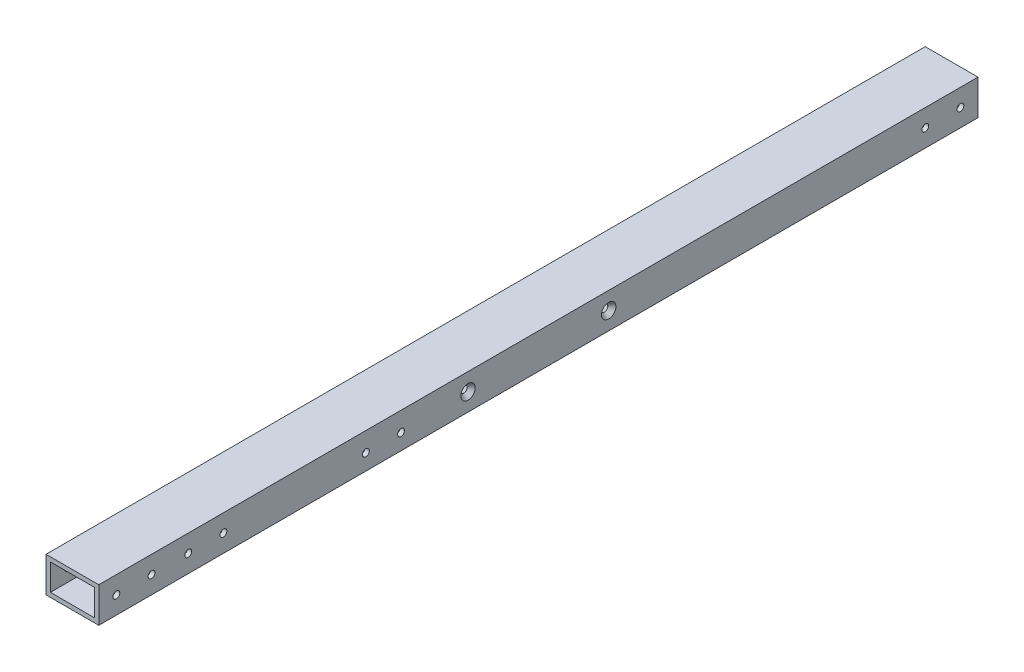
SolidWorks part; units mm, degrees
ref_plane "Front Plane" through (0, 0, 0) normal (0, 0, 1) x (1, 0, 0)
ref_plane "Top Plane" through (0, 0, 0) normal (0, 1, 0) x (1, 0, 0)
ref_plane "Right Plane" through (0, 0, 0) normal (1, 0, 0) x (0, 0, -1)
sketch "Sketch1" plane through (0, 0, 0) normal (0, 0, 1) x (1, 0, 0)
  line L0 (-15.875, 9.525) -> (15.875, 9.525)
  line L2 (-19.05, 12.7) -> (19.05, 12.7)
  line L3 (-19.05, 12.7) -> (-19.05, -12.7)
  line L4 (-19.05, -12.7) -> (19.05, -12.7)
  line L5 (19.05, 12.7) -> (19.05, -12.7)
  line L10 (15.875, 9.525) -> (15.875, -9.525)
  line L11 (-15.875, -9.525) -> (15.875, -9.525)
  line L12 (-15.875, 9.525) -> (-15.875, -9.525)
  point P12 (0, 12.7)
  point P14 (19.05, 0)
  dimension "Wall Thickness" = 3.175
  dimension "Outside Width" = 38.1
  dimension "Outside Height" = 25.4
  dimension "Inside Height" = 19.05
  dimension "Inside Width" = 31.75
sketch "Sketch2" plane through (0, 0, 0) normal (1, 0, 0) x (0, 0, -1)
  line L0 (317.5, 0) -> (-317.5, 0)
  point P4 (0, 0)
  point P7 (-317.5, 0)
  point P10 (317.5, 0)
  dimension "Length" = 635
sketch "Sketch3" plane through (0, 0, 0) normal (0, 0, 1) x (1, 0, 0)
  line L21 (19.05, 12.7) -> (-19.05, 12.7)
  line L22 (19.05, -12.7) -> (19.05, 12.7)
  line L23 (-19.05, -12.7) -> (19.05, -12.7)
  line L24 (-19.05, 12.7) -> (-19.05, -12.7)
  line L25 (19.05, 12.7) -> (-19.05, 12.7)
  line L26 (19.05, -12.7) -> (19.05, 12.7)
  line L27 (-19.05, -12.7) -> (19.05, -12.7)
  line L28 (-19.05, 12.7) -> (-19.05, -12.7)
  line L29 (15.875, 9.525) -> (-15.875, 9.525)
  line L30 (15.875, -9.525) -> (15.875, 9.525)
  line L31 (-15.875, -9.525) -> (15.875, -9.525)
  line L32 (-15.875, 9.525) -> (-15.875, -9.525)
  line L33 (15.875, 9.525) -> (-15.875, 9.525)
  line L34 (15.875, -9.525) -> (15.875, 9.525)
  line L35 (-15.875, -9.525) -> (15.875, -9.525)
  line L36 (-15.875, 9.525) -> (-15.875, -9.525)
  dimension "D1" = 0
  dimension "D2" = 0
extrude "Boss-Extrude1" add sketch "Sketch3" along normal up to vertex (317.5 mm away) and the other way up to vertex (317.5 mm away) up to point (0, 0, 317.5) other way up to point (0, 0, -317.5)
sketch "Drawing Reference" plane through (0, 0, 0) normal (1, 0, 0) x (0, 0, -1)
  line L0 (-317.5, 0) -> (317.5, 0) construction
  line L1 (0, -12.7) -> (0, 12.7) construction
  line L2 (-317.5, -12.7) -> (317.5, -12.7) construction
  line L5 (-317.5, 12.7) -> (317.5, 12.7) construction
  point P7 (-290.068, 0)
  point P8 (290.068, 0)
  dimension "D1" = 27.432
sketch "Sketch4" plane through (-19.05, 0, 0) normal (-1, 0, 0) x (0, 0, 1)
  line L0 (-317.5, 0) -> (-304.8, 0)
  line L1 (-317.5, 12.7) -> (-317.5, -12.7) construction
  line L2 (-304.8, 0) -> (-279.4, 0)
  line L3 (317.5, 12.7) -> (317.5, -12.7) construction
  line L4 (317.5, 0) -> (304.8, 0)
  line L5 (304.8, 0) -> (279.4, 0)
  line L6 (0, 0) -> (50.8, 0) construction
  line L7 (0, 0) -> (-50.8, 0) construction
  point P11 (-304.8, 0)
  point P13 (-279.4, 0)
  point P14 (304.8, 0)
  point P15 (279.4, 0)
hole_wizard "#10 Clearance Hole2" positions "Sketch11" profile "Sketch12" hole size "#10" standard "ANSI Inch" end condition through all
sketch "Sketch11" plane through (-19.05, 0, 0) normal (-1, 0, 0) x (0, 0, 1)
  point P0 (-304.8, 0)
  point P3 (-279.4, 0)
  point P6 (279.4, 0)
  point P9 (304.8, 0)
sketch "Sketch12" plane through (-19.05, 0, -304.8) normal (0, 1, 0) x (0, 0, 1)
  line L0 (0, 0) -> (0, 38.1)
  line L1 (0, 38.1) -> (2.4892, 38.1)
  line L2 (2.4892, 38.1) -> (2.4892, 0)
  line L5 (2.4892, 0) -> (0, 0)
  line L11 (0, -6.35) -> (0, 107.95) construction
  dimension "Thru Hole Dia." = 4.9784
  dimension "Thru Hole Depth" = 38.1
hole_wizard "#10 Clearance Hole5" positions "Sketch14" profile "Sketch16" hole size "#10" standard "ANSI Inch" end condition through all
sketch "Sketch14" plane through (19.05, 0, 0) normal (1, 0, 0) x (0, 0, -1)
  point P10 (-124.587, -1.2316)
  point P13 (-99.187, -1.2316)
  point P17 (-252.857, 0)
  point P20 (-227.457, 0)
sketch "Sketch16" plane through (19.05, -1.2316, 124.587) normal (0, 1, 0) x (0, 0, -1)
  line L0 (0, 0) -> (0, 38.1)
  line L1 (0, 38.1) -> (2.4892, 38.1)
  line L2 (2.4892, 38.1) -> (2.4892, 0)
  line L5 (2.4892, 0) -> (0, 0)
  line L11 (0, -6.35) -> (0, 107.95) construction
  dimension "Thru Hole Dia." = 4.9784
  dimension "Thru Hole Depth" = 38.1
sketch "Sketch17" plane through (19.05, 0, 0) normal (1, 0, 0) x (0, 0, -1)
  point P0 (-252.857, 0)
  point P1 (-227.457, 0)
hole_wizard "#10 Clearance Hole4" positions "Sketch18" profile "Sketch19" hole size "#10" standard "ANSI Inch" end condition through all
sketch "Sketch18" plane through (19.05, 0, 0) normal (1, 0, 0) x (0, 0, -1)
  point P0 (-252.857, 0)
  point P3 (-227.457, 0)
sketch "Sketch19" plane through (19.05, 0, 252.857) normal (0, 1, 0) x (0, 0, -1)
  line L0 (0, 0) -> (0, 38.1)
  line L1 (0, 38.1) -> (2.4892, 38.1)
  line L2 (2.4892, 38.1) -> (2.4892, 0)
  line L5 (2.4892, 0) -> (0, 0)
  line L11 (0, -6.35) -> (0, 107.95) construction
  dimension "Thru Hole Dia." = 4.9784
  dimension "Thru Hole Depth" = 38.1
hole_wizard "#10 Clearance Hole3" positions "Sketch20" profile "Sketch21" hole size "#10" standard "ANSI Inch" end condition through all
sketch "Sketch20" plane through (-19.05, 0, 0) normal (-1, 0, 0) x (0, 0, 1)
  point P0 (-50.8, 0)
  point P3 (50.8, 0)
sketch "Sketch21" plane through (-19.05, 0, -50.8) normal (0, 1, 0) x (0, 0, 1)
  line L0 (0, 0) -> (0, 38.1)
  line L1 (0, 38.1) -> (5.207, 38.1)
  line L2 (2.4892, 34.9735) -> (2.4892, 0)
  line L5 (2.4892, 0) -> (0, 0)
  line L7 (5.207, 38.1) -> (2.4892, 34.9735)
  line L8 (-5.207, 38.1) -> (-2.4892, 34.9735) construction
  line L11 (0, -6.35) -> (0, 107.95) construction
  dimension "Thru Hole Dia." = 4.9784
  dimension "Thru Hole Depth" = 38.1
  dimension "Far C'Sink Dia." = 10.414
  dimension "Far C'Sink Angle" = 82
equation "\"D1@Drawing Reference\"=\"Outside Width@Sketch1\" * 0.72"
